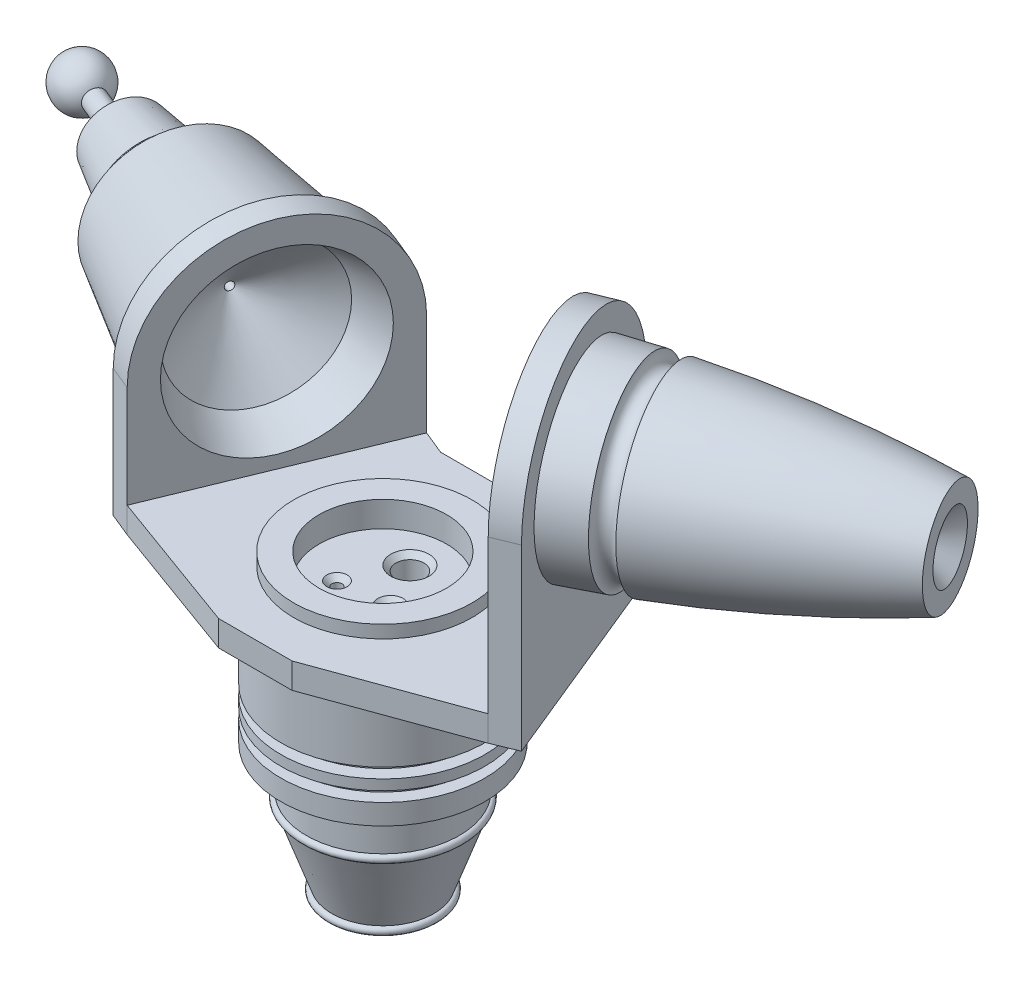
SolidWorks part; units mm, degrees
ref_plane "Front Plane" through (0, 0, 0) normal (0, 0, 1) x (1, 0, 0)
ref_plane "Top Plane" through (0, 0, 0) normal (0, 1, 0) x (1, 0, 0)
ref_plane "Right Plane" through (0, 0, 0) normal (1, 0, 0) x (0, 0, -1)
sketch "Sketch1" plane through (0, 0, 0) normal (0, 0, 1) x (1, 0, 0)
  line L0 (0, 0) -> (25.4, 0)
  line L1 (25.4, 0) -> (25.4, -19.05)
  line L2 (25.4, -19.05) -> (22.225, -19.05)
  line L3 (22.225, -19.05) -> (22.225, -21.59)
  line L4 (22.225, -21.59) -> (25.4, -21.59)
  line L5 (25.4, -21.59) -> (25.4, -24.13)
  line L6 (25.4, -24.13) -> (22.225, -24.13)
  line L7 (22.225, -24.13) -> (22.225, -26.67)
  line L8 (22.225, -26.67) -> (25.4, -26.67)
  line L9 (25.4, -26.67) -> (25.4, -31.75)
  line L10 (25.4, -31.75) -> (19.05, -31.75)
  line L11 (19.05, -31.75) -> (19.05, -42.2275)
  line L13 (12.7, -64.135) -> (0, -64.135)
  line L14 (0, -64.135) -> (0, 0)
  line L15 (12.7, -62.23) -> (19.05, -44.1325)
  arc A0 (19.05, -44.1325) -> (19.05, -42.2275) centre (19.05, -43.18) ccw
  arc A2 (12.7, -64.135) -> (12.7, -62.23) centre (12.7, -63.1825) ccw
  point P3 (23.8125, -24.13)
  dimension "D10" = 20.955
  dimension "D11" = 1.905
  dimension "D13" = 1.905
  dimension "D1" = 64.135
  dimension "D2" = 25.4
  dimension "D3" = 22.225
  dimension "D4" = 19.05
  dimension "D5" = 21.59
  dimension "D6" = 24.13
  dimension "D7" = 26.67
  dimension "D8" = 31.75
  dimension "D9" = 19.05
  dimension "D12" = 12.7
revolve "Revolve1" add sketch "Sketch1" angle 360 about L14
sketch "Sketch2" plane through (0, 0, 0) normal (0, 1, 0) x (1, 0, 0)
  line L0 (-17.3905, 31.75) -> (17.3905, 31.75)
  line L1 (17.3905, 31.75) -> (23.2658, 34.1589)
  line L2 (23.2658, 34.1589) -> (44.9463, -18.719)
  line L3 (44.9463, -18.719) -> (9.144, -31.75)
  line L4 (9.144, -31.75) -> (-9.144, -31.75)
  line L5 (-9.144, -31.75) -> (-44.9463, -18.719)
  line L6 (-44.9463, -18.719) -> (-23.2658, 34.1589)
  line L7 (-23.2658, 34.1589) -> (-17.3905, 31.75)
  line L8 (0, 31.75) -> (0, -31.75) construction
  point P11 (0, 31.75)
  point P12 (0, -31.75)
  point P13 (0, 0)
  dimension "D2" = 6.35
  dimension "D3" = 6.35
  dimension "D4" = 57.15
  dimension "D5" = 57.15
  dimension "D6" = 20
  dimension "D7" = 20
  dimension "D8" = 38.1
  dimension "D9" = 38.1
  dimension "D1" = 18.288
  dimension "D10" = 31.75
extrude "Boss-Extrude1" add sketch "Sketch2" along normal blind 6.35
sketch "Sketch3" plane through (31.9074, 0, -13.0823) normal (0.9252, 0, -0.3794) x (-0.3794, 0, -0.9252)
  line L2 (-34.3706, 44.45) -> (-34.3706, 0)
  line L3 (22.7794, 0) -> (22.7794, 44.45)
  line L4 (-34.3706, 6.35) -> (-34.3706, 0) construction
  line L5 (-34.3706, 0) -> (22.7794, 0)
  line L6 (-25.4, 0) -> (25.4, 0) construction
  line L7 (-34.3706, 0) -> (22.7794, 0) construction
  arc A1 (22.7794, 44.45) -> (-34.3706, 44.45) centre (-5.7956, 44.45) ccw
  point P2 (-35.0835, 37.7122)
  point P3 (1.6142, 36.9159)
  dimension "D1" = 57.15
  dimension "D2" = 44.45
extrude "Boss-Extrude2" add sketch "Sketch3" along normal blind 6.35
sketch "Sketch4" plane through (-31.9074, 0, -13.0823) normal (-0.9252, 0, -0.3794) x (-0.3794, 0, 0.9252)
  line L0 (34.3706, 0) -> (34.3706, 31.75)
  line L1 (34.3706, 0) -> (-22.7794, 0)
  line L2 (-22.7794, 0) -> (-22.7794, 31.75)
  arc A0 (34.3706, 31.75) -> (-22.7794, 31.75) centre (5.7956, 31.75) ccw
  point P5 (34.3706, 31.75)
  point P9 (0, 0)
  dimension "D1" = 57.15
  dimension "D2" = 31.75
extrude "Boss-Extrude3" add sketch "Sketch4" along normal blind 6.35
ref_plane "Plane1" through (2.1986, 0, 5.3624) normal (0.3794, 0, 0.9252) x (0.9252, 0, -0.3794)
sketch "Sketch6" plane through (2.1986, 0, 5.3624) normal (0.3794, 0, 0.9252) x (0.9252, 0, -0.3794)
  line L0 (40.8352, 44.45) -> (40.8352, 67.31) construction
  line L1 (40.8352, 44.45) -> (40.8352, 0) construction
  line L2 (40.8352, 44.45) -> (40.8352, 73.025) construction
  line L3 (40.8352, 44.45) -> (110.6852, 44.45) construction
  line L4 (110.6852, 46.355) -> (110.6852, 57.15)
  line L5 (40.8352, 73.025) -> (34.4852, 73.025) construction
  line L7 (40.8352, 64.77) -> (40.8352, 67.31)
  line L8 (110.6852, 46.355) -> (60.4191, 49.87)
  arc A0 (110.6852, 57.15) -> (56.0674, 66.4132) centre (29.4229, -256.3389) ccw
  arc A1 (51.0016, 66.7914) -> (56.0674, 66.4132) centre (53.5352, 66.6123) ccw
  arc A2 (51.0016, 66.7914) -> (40.8352, 67.31) centre (29.4229, -256.3389) ccw
  arc A3 (60.4191, 49.87) -> (40.8352, 64.77) centre (40.8352, 44.45) ccw
  dimension "D1" = 647.7
  dimension "D2" = 12.7
  dimension "D6" = 12.7
  dimension "D7" = 5.08
  dimension "D8" = 1.905
  dimension "D9" = 40.64
  dimension "D3" = 28.575
  dimension "D4" = 22.86
  dimension "D5" = 69.85
  dimension "D10" = 4
revolve "Revolve2" add sketch "Sketch6" angle 360 about L3
sketch "Sketch7" plane through (2.1986, 0, 5.3624) normal (0.3794, 0, 0.9252) x (0.9252, 0, -0.3794)
  line L0 (34.4852, 44.45) -> (34.4852, 6.35) construction
  line L1 (110.6852, 44.45) -> (34.4852, 44.45)
  line L2 (110.6852, 42.545) -> (110.6852, 46.355) construction
  line L3 (110.6852, 44.45) -> (110.6852, 46.355)
  line L4 (110.6852, 46.355) -> (53.938, 50.3232)
  line L5 (34.4852, 44.45) -> (34.4852, 64.77)
  arc A0 (53.938, 50.3232) -> (34.4852, 64.77) centre (34.4852, 44.45) ccw
  point P1 (0, 0)
  dimension "D1" = 40.64
  dimension "D2" = 1.905
  dimension "D3" = 4
revolve "Cut-Revolve1" cut sketch "Sketch7" angle 360 about L1
chamfer "Chamfer1" distance 6.35 angle 45 2 edges at (60.1574, 44.45, -12.5434) (105.3327, 44.45, -34.8646) first distance on face at (60.1574, 44.45, -12.5434) first distance on face at (105.3327, 44.45, -34.8646)
ref_plane "Plane2" through (-2.1986, 0, 5.3624) normal (0.3794, 0, -0.9252) x (-0.9252, 0, -0.3794)
sketch "Sketch8" plane through (-2.1986, 0, 5.3624) normal (0.3794, 0, -0.9252) x (-0.9252, 0, -0.3794)
  line L0 (40.8352, 57.15) -> (78.9352, 51.1156)
  line L1 (40.8352, 31.75) -> (40.8352, 60.325) construction
  line L2 (78.9352, 51.1156) -> (78.9352, 48.895)
  line L3 (78.9352, 48.895) -> (82.1102, 48.3921)
  line L4 (82.1102, 48.3921) -> (82.1102, 46.355)
  line L5 (82.1102, 46.355) -> (85.2852, 45.847)
  line L6 (85.2852, 45.847) -> (85.2852, 43.815)
  line L7 (85.2852, 43.815) -> (104.3352, 40.7162)
  line L8 (104.3352, 40.7162) -> (104.3352, 34.29)
  line L9 (104.3352, 34.29) -> (117.5654, 34.29)
  line L11 (123.3852, 31.75) -> (40.8352, 31.75)
  line L12 (40.8352, 31.75) -> (40.8352, 0) construction
  line L13 (40.8352, 31.75) -> (40.8352, 57.15)
  line L14 (123.3852, 31.75) -> (129.7352, 31.75)
  arc A0 (129.7352, 31.75) -> (117.5654, 34.29) centre (123.3852, 31.75) ccw
  dimension "D15" = 12.7
  dimension "D1" = 82.55
  dimension "D2" = 63.5
  dimension "D3" = 44.45
  dimension "D4" = 41.275
  dimension "D5" = 38.1
  dimension "D6" = 2.54
  dimension "D7" = 8.9662
  dimension "D8" = 12.065
  dimension "D9" = 14.097
  dimension "D10" = 25.4
  dimension "D11" = 28.575
  dimension "D12" = 17.145
  dimension "D13" = 9
  dimension "D14" = 14.605
revolve "Revolve3" add sketch "Sketch8" angle 360 about L11
sketch "Sketch9" plane through (-2.1986, 0, 5.3624) normal (0.3794, 0, -0.9252) x (-0.9252, 0, -0.3794)
  line L0 (34.4852, 53.975) -> (44.0102, 49.9966)
  line L1 (34.4852, 60.325) -> (34.4852, 31.75) construction
  line L2 (44.0102, 49.9966) -> (56.0752, 32.766)
  line L3 (56.0752, 32.766) -> (129.7352, 32.766)
  line L4 (129.7352, 32.766) -> (129.7352, 31.75)
  line L5 (129.7352, 31.75) -> (34.4852, 31.75)
  line L6 (34.4852, 31.75) -> (34.4852, 53.975)
  point P4 (44.0102, 53.0119)
  dimension "D1" = 1.016
  dimension "D2" = 55
  dimension "D3" = 9.525
  dimension "D4" = 22.225
  dimension "D5" = 21.59
  dimension "D6" = 95.25
revolve "Cut-Revolve2" cut sketch "Sketch9" angle 360 about L5
sketch "Sketch11" plane through (0, 6.35, 0) normal (0, 1, 0) x (1, 0, 0)
  circle A1 centre (0, 0) radius 22.225
  dimension "D2" = 44.45
extrude "Boss-Extrude4" add sketch "Sketch11" along normal blind 3.175
sketch "Sketch12" plane through (0, 9.525, 0) normal (0, 1, 0) x (1, 0, 0)
  circle A0 centre (0, 0) radius 15.875
  dimension "D1" = 31.75
extrude "Cut-Extrude2" cut sketch "Sketch12" against normal blind 6.35
sketch "Sketch10" plane through (0, 6.35, 0) normal (0, 1, 0) x (1, 0, 0)
  circle A0 centre (0, 6.731) radius 3.4925
  circle A1 centre (6.35, -4.445) radius 1.905
  circle A2 centre (-5.715, -5.715) radius 1.27
  point P7 (0, 0)
  point P11 (6.929, -6.2146)
  dimension "D1" = 6.731
  dimension "D6" = 2.54
  dimension "D7" = 3.81
  dimension "D8" = 6.985
  dimension "D2" = 6.35
  dimension "D3" = 4.445
  dimension "D4" = 5.715
  dimension "D5" = 5.715
extrude "Cut-Extrude1" cut sketch "Sketch10" against normal through all
chamfer "Chamfer2" distance 1.27 angle 45 6 edges at (-5.715, -64.135, 6.985) (6.35, -64.135, 6.35) (0, -64.135, -3.2385) (6.35, 3.175, 6.35) (0, 3.175, -3.2385) (-5.715, 3.175, 6.985)
equation "\"D5@Sketch2\"=\"D4@Sketch2\""
equation "\"D7@Sketch2\"=\"D6@Sketch2\""
